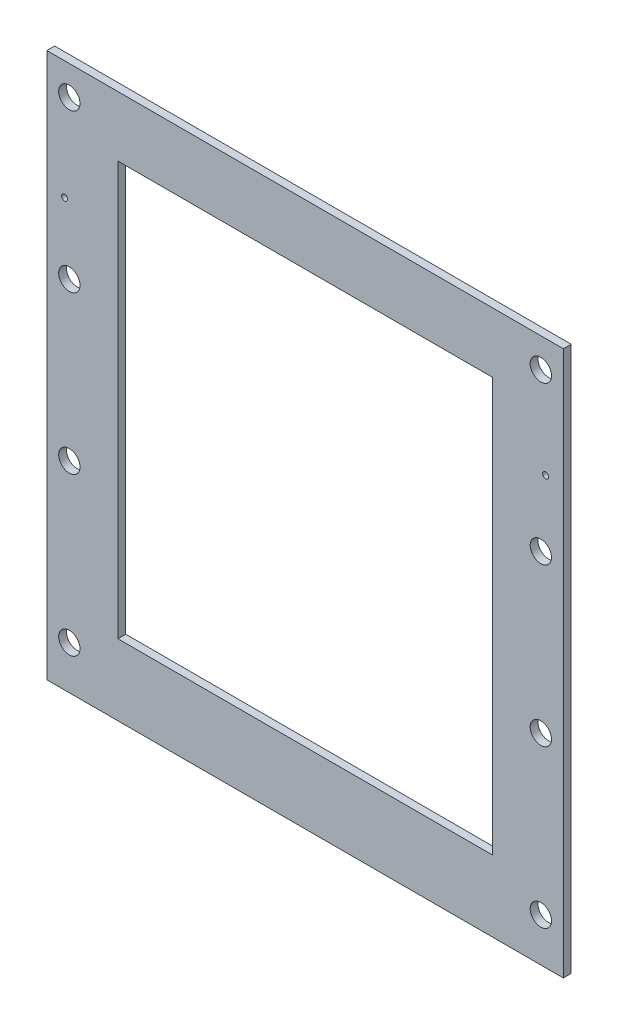
SolidWorks part; units mm, degrees
ref_plane "Front Plane" through (0, 0, 0) normal (0, 0, 1) x (1, 0, 0)
ref_plane "Top Plane" through (0, 0, 0) normal (0, 1, 0) x (1, 0, 0)
ref_plane "Right Plane" through (0, 0, 0) normal (1, 0, 0) x (0, 0, -1)
sketch "Sketch1" plane through (0, 0, 0) normal (0, 0, 1) x (1, 0, 0)
  line L0 (81.8848, 109.8822) -> (81.8848, -120.1178)
  line L2 (81.8848, -120.1178) -> (-136.1152, -120.1178)
  line L3 (-136.1152, 109.8822) -> (-136.1152, -120.1178)
  line L4 (-106.1152, 84.4822) -> (-106.1152, -90.1178)
  line L5 (51.8848, -90.1178) -> (-106.1152, -90.1178)
  line L6 (51.8848, 84.4822) -> (51.8848, -90.1178)
  line L8 (81.8848, 159.8822) -> (81.8848, -120.1178) construction
  line L9 (-106.1152, 109.8822) -> (51.8848, 109.8822)
  line L10 (-106.1152, 129.8822) -> (-106.1152, -90.1178) construction
  line L11 (51.8848, 129.8822) -> (-106.1152, 129.8822) construction
  line L12 (51.8848, 129.8822) -> (51.8848, -90.1178) construction
  line L14 (-136.1152, 159.8822) -> (-136.1152, -120.1178) construction
  line L15 (81.8848, 159.8822) -> (-136.1152, 159.8822) construction
  line L17 (-106.1152, 84.4822) -> (51.8848, 84.4822)
  line L18 (51.8848, 109.8822) -> (81.8848, 109.8822)
  line L19 (-106.1152, 109.8822) -> (-136.1152, 109.8822)
  circle A2 centre (-126.6152, 97.4822) radius 4.5
  circle A5 centre (72.3848, 97.4822) radius 4.5
  circle A8 centre (-128.6152, 59.8822) radius 1.25
  circle A9 centre (74.3848, 59.8822) radius 1.25
  circle A13 centre (-126.6152, 31.0622) radius 4.5
  circle A14 centre (72.3848, 31.0622) radius 4.5
  circle A15 centre (-126.6152, -35.3578) radius 4.5
  circle A16 centre (72.3848, -35.3578) radius 4.5
  circle A17 centre (-126.6152, -101.7778) radius 4.5
  circle A18 centre (72.3848, -101.7778) radius 4.5
  dimension "D3" = 4
  dimension "D7" = 9.5
  dimension "D10" = 9.5
  dimension "D11" = 30
  dimension "D12" = 7.5
  dimension "D13" = 7.5
  dimension "D2" = 218
extrude "Boss-Extrude1" add sketch "Sketch1" along normal blind 3.302
